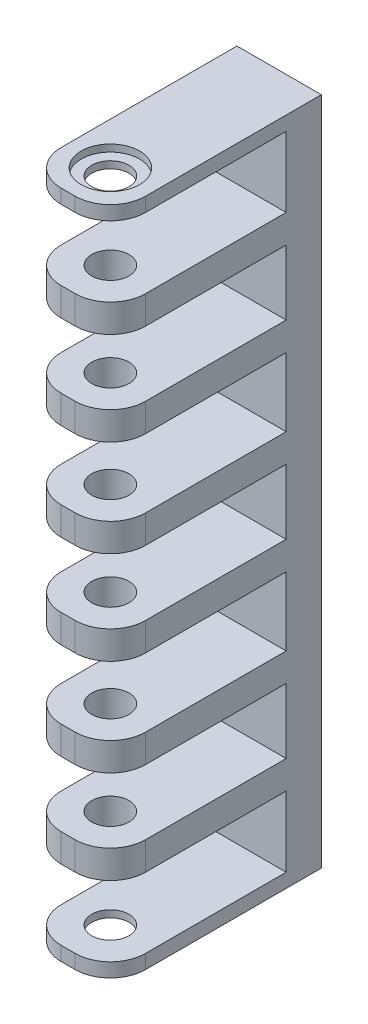
SolidWorks part; units mm, degrees
ref_plane "Front Plane" through (0, 0, 0) normal (1, 0, 0) x (0, 1, 0)
ref_plane "Top Plane" through (0, 0, 0) normal (0, 0, 1) x (0, 1, 0)
ref_plane "Right Plane" through (0, 0, 0) normal (0, 1, 0) x (-1, 0, 0)
sketch "Sketch1" plane through (0, 0, 0) normal (0, 0, 1) x (0, 1, 0)
  line L1 (0, 0) -> (-95.25, 0)
  line L2 (0, 0) -> (0, 12)
  line L3 (0, 12) -> (-95.25, 12)
  line L4 (-95.25, 0) -> (-95.25, 12)
extrude "Boss-Extrude1" add sketch "Sketch1" along normal blind 5 contours L3 L4 L1 L2
sketch "Sketch3" plane through (0, 0, 5) normal (0, 0, 1) x (1, 0, 0)
  line L0 (0, 0) -> (0, -95.25) construction
  line L1 (-12, 0) -> (0, 0)
  line L2 (-12, 0) -> (-12, -2)
  line L3 (-12, -2) -> (0, -2)
  line L4 (0, 0) -> (0, -2)
  line L5 (-12, 0) -> (-12, -95.25) construction
  line L6 (-12, -2) -> (0, -2) construction
  line L7 (-12, -2) -> (-12, -12) construction
  line L8 (-12, -12) -> (0, -12) construction
  line L9 (0, -2) -> (0, -12) construction
  line L10 (-12, -12) -> (0, -12)
  line L11 (-12, -12) -> (-12, -16)
  line L12 (-12, -16) -> (0, -16)
  line L13 (0, -12) -> (0, -16)
  line L14 (-12, -16) -> (0, -16) construction
  line L15 (-12, -16) -> (-12, -25.25) construction
  line L16 (-12, -25.25) -> (0, -25.25) construction
  line L17 (0, -16) -> (0, -25.25) construction
  line L18 (0, -25.25) -> (-12, -25.25)
  line L19 (0, -25.25) -> (0, -29.25)
  line L20 (0, -29.25) -> (-12, -29.25)
  line L21 (-12, -25.25) -> (-12, -29.25)
  line L23 (-12, -29.25) -> (0, -29.25) construction
  line L24 (-12, -29.25) -> (-12, -39) construction
  line L25 (-12, -39) -> (0, -39) construction
  line L26 (0, -29.25) -> (0, -39) construction
  line L27 (-12, -39) -> (0, -39)
  line L28 (-12, -39) -> (-12, -43)
  line L29 (-12, -43) -> (0, -43)
  line L30 (0, -39) -> (0, -43)
extrude "Boss-Extrude2" add sketch "Sketch3" along normal blind 25
fillet "Fillet1" radius 5 8 edges at (-12, -1, 30) (0, -1, 30) (-12, -14, 30) (0, -14, 30) (-12, -41, 30) (-12, -27.25, 30) (0, -27.25, 30) (0, -41, 30)
ref_plane "Plane1" through (0, -47.625, 0) normal (0, 1, 0) x (1, 0, 0)
mirror "Mirror1" about plane through (0, -47.625, 0) normal (0, 1, 0) of "Fillet1", "Boss-Extrude2"
sketch "Sketch5" plane through (0, 0, 0) normal (0, 1, 0) x (-1, 0, 0)
  line L0 (5, 30) -> (7, 30) construction
  line L1 (6, 30) -> (0, 30)
  line L2 (6, 30) -> (6, 24)
  line L3 (6, 24) -> (0, 24)
  line L4 (0, 30) -> (0, 24)
  circle A0 centre (6, 24) radius 2.65
  point P8 (0, 0)
extrude "Cut-Extrude1" cut sketch "Sketch5" against normal through all contours A0
sketch "Sketch7" plane through (0, 0, 0) normal (0, 1, 0) x (-1, 0, 0)
  line L0 (5, 30) -> (7, 30) construction
  line L1 (6, 30) -> (0, 30)
  line L2 (6, 30) -> (6, 24)
  line L3 (6, 24) -> (0, 24)
  line L4 (0, 30) -> (0, 24)
  line L5 (0, 25) -> (0, 0) construction
  circle A0 centre (6, 24) radius 4.15
  circle M6 centre (6, 24) radius 2.65
extrude "Cut-Extrude2" cut sketch "Sketch7" against normal blind 1 contours L3 A0 L2 M6 | L2 A0 L3 M6 region at (-8.8515, 0, 26.8515) region at (-3.8004, 0, 26.1996)
mirror "Mirror2" about plane through (0, -47.625, 0) normal (0, 1, 0) of "Cut-Extrude2"
